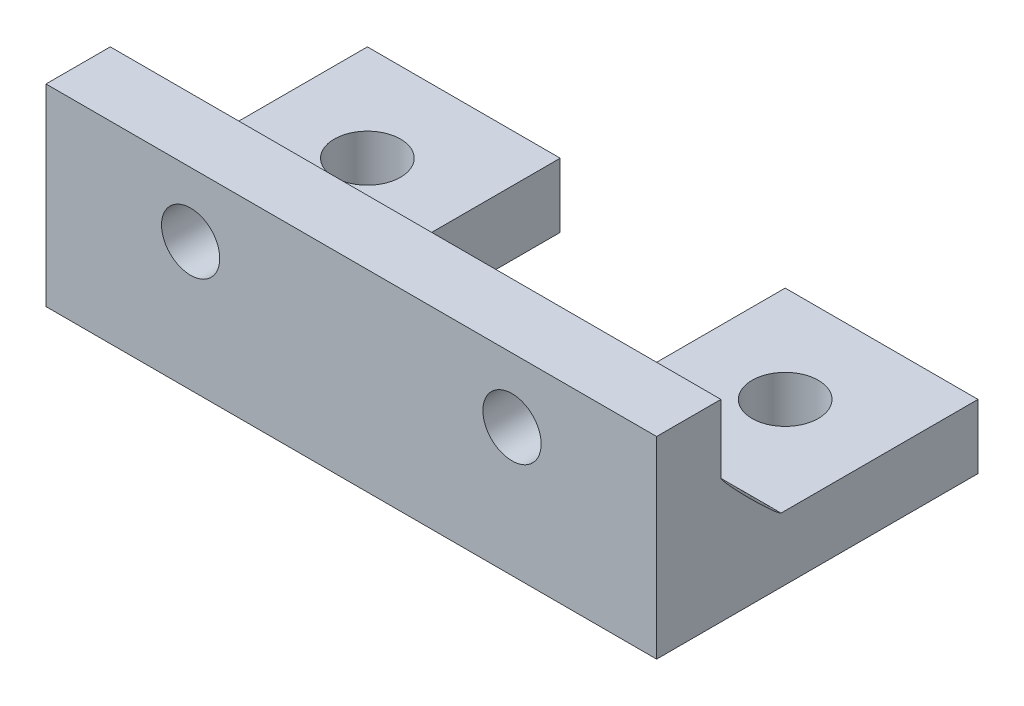
SolidWorks part; units mm, degrees
ref_plane "Front Plane" through (0, 0, 0) normal (0, 0, 1) x (1, 0, 0)
ref_plane "Top Plane" through (0, 0, 0) normal (0, 1, 0) x (1, 0, 0)
ref_plane "Right Plane" through (0, 0, 0) normal (1, 0, 0) x (0, 0, -1)
sketch "Sketch1" plane through (0, 0, 0) normal (0, 1, 0) x (1, 0, 0)
  line L1 (0, 0) -> (30.4, 0)
  line L2 (0, 0) -> (0, -6.4)
  line L3 (0, -6.4) -> (30.4, -6.4)
  line L4 (30.4, 0) -> (30.4, -6.4)
  dimension "D1" = 6.4
  dimension "D2" = 30.4
extrude "Boss-Extrude1" add sketch "Sketch1" along normal blind 3.2
sketch "Sketch2" plane through (0, 3.2, 0) normal (0, 1, 0) x (1, 0, 0)
  line L0 (30.4, 0) -> (0, 0) construction
  line L1 (0, 0) -> (9.6, 0)
  line L2 (0, 0) -> (0, 9.6)
  line L3 (0, 9.6) -> (9.6, 9.6)
  line L4 (9.6, 0) -> (9.6, 9.6)
  line L5 (20.8, 0) -> (30.4, 0)
  line L6 (20.8, 0) -> (20.8, 9.6)
  line L7 (20.8, 9.6) -> (30.4, 9.6)
  line L8 (30.4, 0) -> (30.4, 9.6)
  circle A0 centre (4.8, 4.8) radius 1.65
  circle A1 centre (25.6, 4.8) radius 1.65
  dimension "D6" = 3.3
  dimension "D7" = 3.3
  dimension "D1" = 9.6
  dimension "D2" = 9.6
  dimension "D3" = 9.6
  dimension "D4" = 9.6
  dimension "D5" = 11.2
  dimension "D8" = 4.8
  dimension "D9" = 4.8
extrude "Boss-Extrude2" add sketch "Sketch2" against normal blind 3.2
sketch "Sketch3" plane through (0, 3.2, 0) normal (0, 1, 0) x (1, 0, 0)
  line L1 (0, -6.4) -> (30.4, -6.4)
  line L2 (0, -6.4) -> (0, -3.2)
  line L3 (0, -3.2) -> (30.4, -3.2)
  line L4 (30.4, -6.4) -> (30.4, -3.2)
  dimension "D2" = 30.4
  dimension "D1" = 3.2
extrude "Boss-Extrude3" add sketch "Sketch3" along normal blind 6.4
fillet "Fillet2" radius 3 1 edges at (15.2, 3.2, 3.2) conic rho 0.05
sketch "Sketch4" plane through (0, 0, 6.4) normal (0, 0, 1) x (1, 0, 0)
  line L0 (0, 9.6) -> (0, 0) construction
  line L1 (0, 0) -> (30.4, 0) construction
  circle A0 centre (7.2, 6.4) radius 1.45
  circle A1 centre (23.2, 6.4) radius 1.45
  dimension "D1" = 2.9
  dimension "D2" = 2.9
  dimension "D3" = 7.2
  dimension "D4" = 16
  dimension "D5" = 6.4
  dimension "D6" = 6.4
extrude "Cut-Extrude1" cut sketch "Sketch4" against normal blind 24
ref_plane "Plane1" through (0, 0, -0.8) normal (0, 0, -1) x (-1, 0, 0)
sketch "Sketch5" plane through (0, 0, -0.8) normal (0, 0, -1) x (-1, 0, 0)
  circle A0 centre (-23.2, 6.4) radius 2.75
  circle A1 centre (-7.2, 6.4) radius 2.75
  dimension "D1" = 5.5
  dimension "D2" = 5.5
extrude "Cut-Extrude2" cut sketch "Sketch5" against normal blind 4
equation "\"滑动-垂直孔\" = 0.6"
equation "\"滑动-水平孔\" = 0.3"
equation "\"松动-垂直孔\" = 0.3"
equation "\"松动-水平孔\" = 0.1"
equation "\"正常-垂直孔\" = 0.15"
equation "\"正常-水平孔\" = 0"
equation "\"紧缩-垂直孔\" = 0"
equation "\"紧缩-水平孔\" = -0.1"
equation "\"_喷嘴物理宽度\" = 0.8"
equation "\"_喷嘴宽度系数\" = 1"
equation "\"_物理厚度\" = 0.4"
equation "\"_物理厚度系数\" = 2"
equation "\"喷嘴宽度\" = \"_喷嘴物理宽度\" * \"_喷嘴宽度系数\""
equation "\"喷嘴厚度\" = \"_物理厚度\" * \"_物理厚度系数\""
equation "\"D1@Sketch1\"=\"喷嘴宽度\"*8"
equation "\"D2@Sketch1\"=\"喷嘴宽度\"*38"
equation "\"D1@Boss-Extrude1\"=\"喷嘴厚度\"*4"
equation "\"D1@Sketch2\"=\"喷嘴宽度\"*12"
equation "\"D2@Sketch2\"=\"D1@Sketch2\""
equation "\"D3@Sketch2\"=\"D1@Sketch2\""
equation "\"D4@Sketch2\"=\"D3@Sketch2\""
equation "\"D5@Sketch2\"=\"喷嘴宽度\"*12 + \"喷嘴宽度\"*2"
equation "\"D1@Boss-Extrude2\"=\"喷嘴宽度\"*4"
equation "\"D6@Sketch2\"=\"松动-垂直孔\"+3"
equation "\"D7@Sketch2\"=\"D6@Sketch2\""
equation "\"D1@Sketch3\"=\"喷嘴宽度\"*4"
equation "\"D2@Sketch3\"=\"喷嘴宽度\"*38"
equation "\"D1@Boss-Extrude3\"=\"喷嘴宽度\"*8"
equation "\"D1@Sketch4\"=\"紧缩-水平孔\"+3"
equation "\"D2@Sketch4\"=\"D1@Sketch4\""
equation "\"D4@Sketch4\"=\"喷嘴宽度\"*20"
equation "\"D3@Sketch4\"=\"喷嘴宽度\"*9"
equation "\"D5@Sketch4\"=\"D6@Sketch4\""
equation "\"D6@Sketch4\"=\"喷嘴宽度\"*8"
equation "\"D8@Sketch2\"=\"D4@Sketch2\"/2"
equation "\"D9@Sketch2\"=\"D1@Sketch2\"/2"
